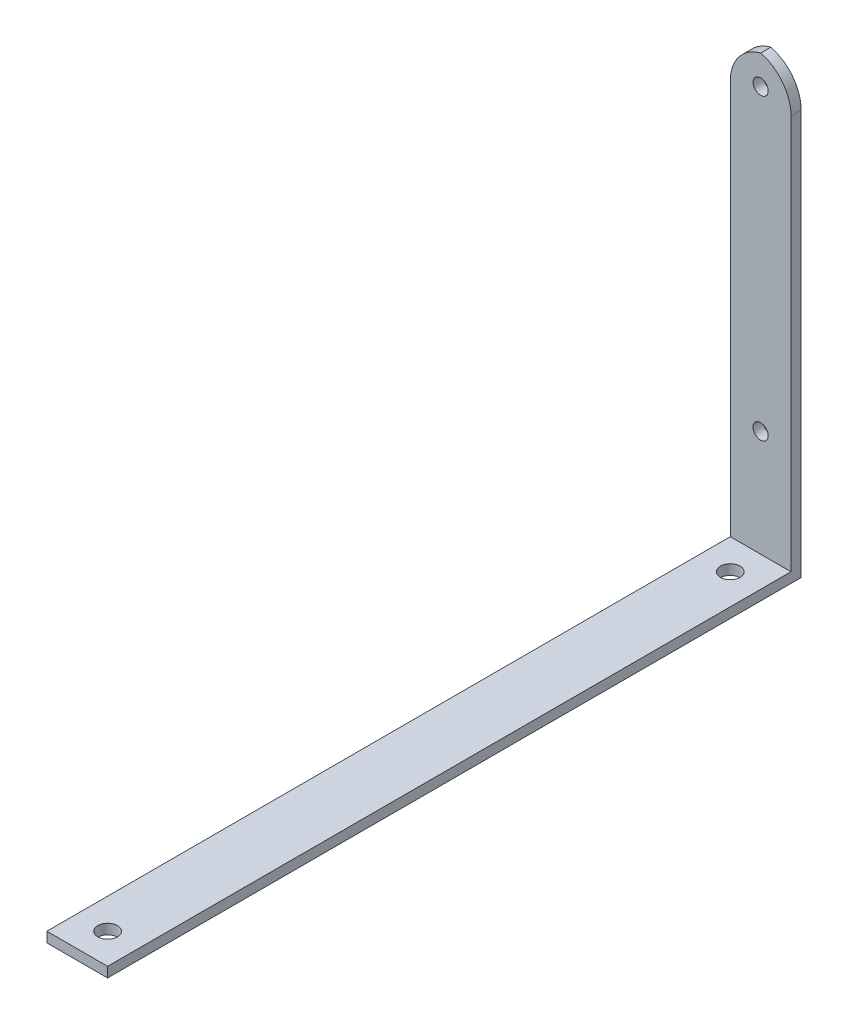
SolidWorks part; units mm, degrees
ref_plane "Front Plane" through (0, 0, 0) normal (0, 0, 1) x (1, 0, 0)
ref_plane "Top Plane" through (0, 0, 0) normal (0, 1, 0) x (1, 0, 0)
ref_plane "Right Plane" through (0, 0, 0) normal (1, 0, 0) x (0, 0, -1)
sketch "Sketch1" plane through (0, 0, 0) normal (0, 0, 1) x (1, 0, 0)
  line L1 (0, 0) -> (12, 0)
  line L2 (0, 0) -> (0, 88)
  line L3 (0, 88) -> (12, 88)
  line L4 (12, 0) -> (12, 88)
  circle A0 centre (6, 82) radius 1.5
  circle A1 centre (6, 23) radius 1.5
  dimension "D3" = 3
  dimension "D1" = 88
  dimension "D2" = 12
  dimension "D4" = 6
  dimension "D5" = 6
  dimension "D6" = 59
extrude "Boss-Extrude1" add sketch "Sketch1" along normal blind 2
sketch "Sketch2" plane through (0, 0, 2) normal (0, 0, 1) x (1, 0, 0)
  line L0 (12, 0) -> (12, 88) construction
  line L1 (0, 0) -> (12, 0)
  line L2 (0, 0) -> (0, 2)
  line L3 (0, 2) -> (12, 2)
  line L4 (12, 0) -> (12, 2)
  dimension "D1" = 2
extrude "Boss-Extrude2" add sketch "Sketch2" along normal blind 135
fillet "Fillet1" radius 8 2 edges at (12, 88, 1) (0, 88, 1)
sketch "Sketch3" plane through (0, 2, 0) normal (0, 1, 0) x (1, 0, 0)
  line L0 (12, -137) -> (0, -137) construction
  line L1 (12, -2) -> (0, -2) construction
  line L2 (0, -137) -> (0, -2) construction
  circle A0 centre (6, -131) radius 1.9394
  circle A1 centre (6, -8) radius 1.9394
  dimension "D1" = 6
  dimension "D2" = 6
  dimension "D3" = 6
extrude "Cut-Extrude1" cut sketch "Sketch3" against normal through all
